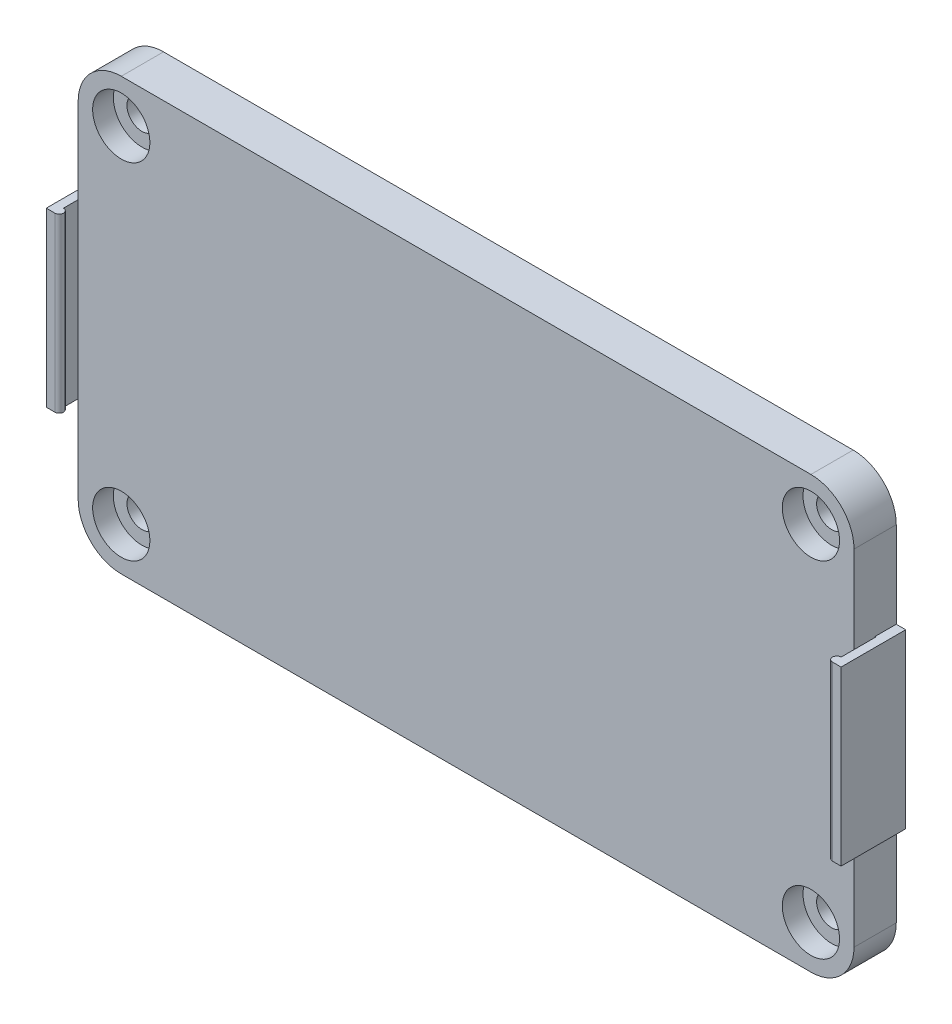
SolidWorks part; units mm, degrees
material "ABS"
ref_plane "Front Plane" through (0, 0, 0) normal (0, 0, 1) x (1, 0, 0)
ref_plane "Top Plane" through (0, 0, 0) normal (0, 1, 0) x (1, 0, 0)
ref_plane "Right Plane" through (0, 0, 0) normal (1, 0, 0) x (0, 0, -1)
sketch "Sketch1" plane through (0, 0, 0) normal (0, 0, 1) x (1, 0, 0)
  line L1 (-50.8, -31.75) -> (50.8, -31.75)
  line L2 (-57.15, -25.4) -> (-57.15, 25.4)
  line L3 (-50.8, 31.75) -> (50.8, 31.75)
  line L4 (57.15, -25.4) -> (57.15, 25.4)
  line L5 (-57.15, -31.75) -> (57.15, 31.75) construction
  line L6 (-57.15, 31.75) -> (57.15, -31.75) construction
  arc A0 (50.8, -31.75) -> (57.15, -25.4) centre (50.8, -25.4) ccw
  arc A1 (50.8, 31.75) -> (57.15, 25.4) centre (50.8, 25.4) cw
  arc A2 (-57.15, 25.4) -> (-50.8, 31.75) centre (-50.8, 25.4) cw
  arc A3 (-50.8, -31.75) -> (-57.15, -25.4) centre (-50.8, -25.4) cw
  circle A4 centre (-50.8, -25.4) radius 2.2098
  circle A5 centre (-50.8, 25.4) radius 2.2098
  circle A6 centre (50.8, 25.4) radius 2.2098
  circle A7 centre (50.8, -25.4) radius 2.2098
  point P0 (0, 0)
  dimension "D3" = 6.35
  dimension "D4" = 4.4196
  dimension "D1" = 114.3
  dimension "D2" = 63.5
extrude "Boss-Extrude1" add sketch "Sketch1" along normal blind 6.223
sketch "Sketch2" plane through (0, 0, 6.223) normal (0, 0, 1) x (1, 0, 0)
  circle A0 centre (-50.8, 25.4) radius 4.2164
  circle A1 centre (50.8, 25.4) radius 4.2164
  circle A2 centre (50.8, -25.4) radius 4.2164
  circle A3 centre (-50.8, -25.4) radius 4.2164
  dimension "D1" = 8.4328
extrude "Cut-Extrude1" cut sketch "Sketch2" against normal blind 3.048
sketch "Sketch4" plane through (0, 0, 0) normal (0, 0, 1) x (1, 0, 0)
  line L0 (-57.15, 25.4) -> (-57.15, -25.4) construction
  line L1 (-57.15, 12.7) -> (-58.547, 12.7)
  line L2 (-57.15, 12.7) -> (-57.15, -12.7)
  line L3 (-57.15, -12.7) -> (-58.547, -12.7)
  line L4 (-58.547, 12.7) -> (-58.547, -12.7)
  line L5 (0, -55) -> (0, 55) construction
  line L6 (57.15, -12.7) -> (58.547, -12.7)
  line L7 (58.547, 12.7) -> (58.547, -12.7)
  line L8 (57.15, 12.7) -> (58.547, 12.7)
  line L9 (57.15, 12.7) -> (57.15, -12.7)
  point P6 (-57.15, 0)
  dimension "D1" = 25.4
  dimension "D2" = 1.397
extrude "Boss-Extrude2" add sketch "Sketch4" along normal blind 3.1115
sketch "Sketch5" plane through (0, -12.7, 0) normal (0, -1, 0) x (1, 0, 0)
  line L0 (-57.277, 3.1115) -> (-58.547, 3.1115)
  line L2 (-58.547, 3.1115) -> (-58.547, 9.525)
  line L3 (-58.547, 9.525) -> (-57.277, 9.525)
  line L6 (-57.277, 8.255) -> (-57.277, 3.1115)
  line L12 (-58.547, 3.1115) -> (-57.15, 3.1115) construction
  line L13 (-58.547, 3.1115) -> (-58.547, 0) construction
  line L14 (0, -55) -> (0, 55) construction
  line L15 (58.547, 9.525) -> (57.277, 9.525)
  line L16 (58.547, 3.1115) -> (58.547, 9.525)
  line L17 (57.277, 3.1115) -> (58.547, 3.1115)
  line L18 (57.277, 8.255) -> (57.277, 3.1115)
  arc A0 (-57.277, 9.525) -> (-57.277, 8.255) centre (-57.277, 8.89) cw
  arc A2 (57.277, 9.525) -> (57.277, 8.255) centre (57.277, 8.89) ccw
  point P18 (-56.642, 8.89)
  dimension "D2" = 0.635
  dimension "D1" = 1.27
  dimension "D3" = 5.7785
extrude "Boss-Extrude3" add sketch "Sketch5" against normal up to surface (25.4 mm away) up to face at (-57.8485, 12.7, 1.5557)
equation "\"wall-thickness\"= .2"
equation "\"tolerance\"= 0.005"
equation "\"D1@Boss-Extrude1\"= .115 + .125 + \"tolerance\""
equation "\"D4@Sketch1\"=.164 + \"tolerance\" * 2"
equation "\"D1@Sketch2\"= .322 + \"tolerance\" * 2"
equation "\"D1@Cut-Extrude1\"= .115 + \"tolerance\""
equation "\"D2@Sketch4\"=.05 + \"tolerance\""
equation "\"D3@Sketch5\"=(.125+0.08+\"tolerance\")/2+\"D1@Boss-Extrude2\""
equation "\"D1@Boss-Extrude2\"= \"D1@Boss-Extrude1\" / 2"
